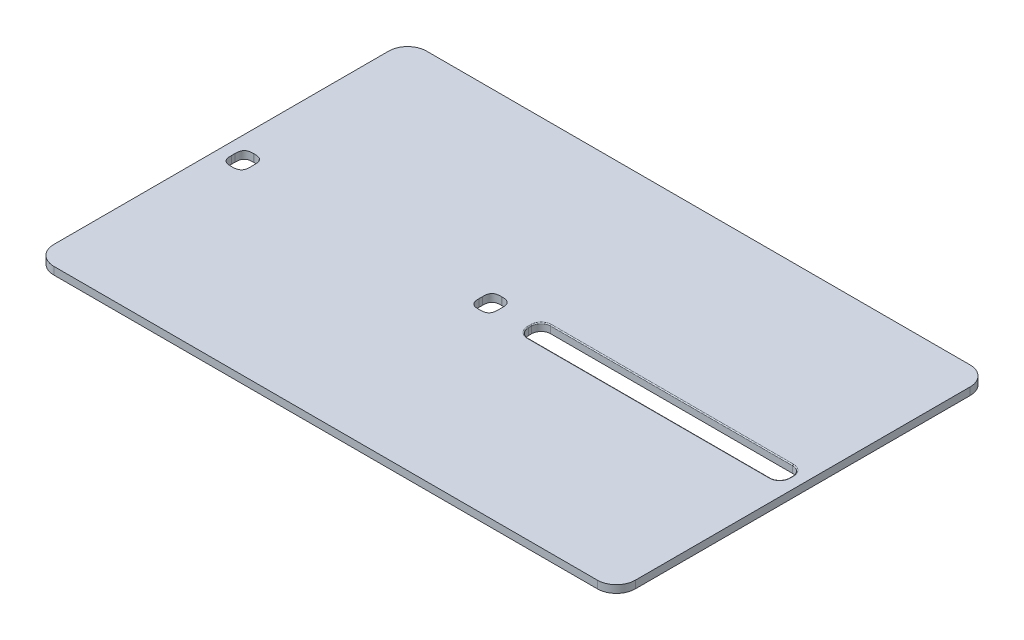
SolidWorks part; units mm, degrees
ref_plane "Front Plane" through (0, 0, 0) normal (0, 0, 1) x (1, 0, 0)
ref_plane "Top Plane" through (0, 0, 0) normal (0, 1, 0) x (1, 0, 0)
ref_plane "Right Plane" through (0, 0, 0) normal (1, 0, 0) x (0, 0, -1)
sketch "Sketch1" plane through (0, 0, 0) normal (0, 1, 0) x (1, 0, 0)
  line L1 (0, 0) -> (78, 0)
  line L2 (0, 0) -> (0, 50)
  line L3 (0, 50) -> (78, 50)
  line L4 (78, 0) -> (78, 50)
  dimension "D1" = 78
  dimension "D2" = 50
extrude "steel_face" add sketch "Sketch1" along normal blind 1.016
fillet "card_edges" radius 2.54 4 edges at (0, 0.508, -50) (78, 0.508, -50) (78, 0.508, 0) (0, 0.508, 0)
sketch "Sketch2" plane through (0, 0, 0) normal (0, -1, 0) x (1, 0, 0)
  line L2 (0, -47.46) -> (0, -2.54) construction
  line L4 (75.46, -50) -> (2.54, -50) construction
  circle A0 centre (4.1275, -45.8725) radius 2.54
  dimension "D1" = 5.08
  dimension "D2" = 1.5875
  dimension "D3" = 1.5875
extrude "magnet_cavity" cut sketch "Sketch2" against normal blind 0.3334
ref_plane "Plane1" through (39, 0, 0) normal (1, 0, 0) x (0, 0, -1)
ref_plane "Plane2" through (0, 0, -25) normal (0, 0, 1) x (1, 0, 0)
mirror "Mirror1" about plane through (0, 0, -25) normal (0, 0, 1) of "magnet_cavity"
mirror "Mirror2" about plane through (39, 0, 0) normal (1, 0, 0) of "Mirror1"
sketch "Sketch3" plane through (0, 0, 0) normal (0, -1, 0) x (1, 0, 0)
  line L0 (2.54, 0) -> (75.46, 0) construction
  line L1 (0, -47.46) -> (0, -2.54) construction
  line L4 (75.46, -50) -> (2.54, -50) construction
  circle A0 centre (16.4, -11.6375) radius 10.05
  circle A1 centre (16.4, -38.3625) radius 10.05
  point P4 (16.4, -36.1176)
  point P5 (14.1387, -35.921)
  point P6 (16.4, -36.5106)
  point P7 (16.4, -37.4334)
  dimension "D2" = 1.5875
  dimension "D1" = 20.1
  dimension "D3" = 6.35
  dimension "D4" = 1.5875
extrude "battery_pockets" cut sketch "Sketch3" against normal blind 0.873
sketch "Sketch5" plane through (0, 0, 0) normal (0, 1, 0) x (1, 0, 0)
  line L0 (78, 2.54) -> (78, 47.46) construction
  line L1 (76.4125, 26.5) -> (41.4125, 26.5)
  line L2 (76.4125, 26.5) -> (76.4125, 23.5)
  line L3 (76.4125, 23.5) -> (41.4125, 23.5)
  line L4 (41.4125, 26.5) -> (41.4125, 23.5)
  line L5 (-0.6138, 25) -> (0.6138, 25) construction
  dimension "D1" = 1.5875
  dimension "D2" = 3
  dimension "D3" = 35
  dimension "D4" = 1.5
extrude "led_slot" cut sketch "Sketch5" along direction (0, -1, 0) on the side of the normal through all
sketch "Sketch4" plane through (0, 0, 0) normal (0, -1, 0) x (1, 0, 0)
  line L0 (7.4613, -48.4125) -> (7.4613, -42.5388)
  line L1 (7.4613, -48.4125) -> (70.5387, -48.4125)
  line L2 (70.5387, -48.4125) -> (70.5387, -42.5388)
  line L3 (1.5875, -27.9199) -> (76.476, -27.9199)
  line L4 (7.4613, -42.5388) -> (1.5875, -42.5388)
  line L5 (1.5875, -42.5388) -> (1.5875, -27.9199)
  line L6 (70.5387, -42.5388) -> (76.476, -42.5388)
  line L7 (76.476, -27.9199) -> (76.476, -42.5388)
  line L8 (0, -47.46) -> (0, -2.54) construction
  line L9 (78, -2.54) -> (78, -47.46) construction
  circle A1 centre (4.1275, -45.8725) radius 2.54 construction
  circle A2 centre (73.8725, -45.8725) radius 2.54 construction
  circle A3 centre (4.1275, -45.8725) radius 2.54 construction
  circle A6 centre (73.8725, -45.8725) radius 2.54 construction
  point P0 (4.1275, -45.8725)
  point P1 (73.8725, -45.8725)
  dimension "D1" = 1.5875
  dimension "D2" = 1.524
  dimension "D3" = 0.7937
  dimension "D4" = 0.7937
  dimension "D5" = 0.7937
  dimension "D6" = 0.7937
extrude "aluminium_inset_hole" [suppressed] cut sketch "Sketch4" against normal through all
fillet "Fillet1" [suppressed] radius 2.54
fillet "led_slot_corner_round" radius 1.27 4 edges at (41.4125, 0.508, -26.5) (41.4125, 0.508, -23.5) (76.4125, 0.508, -26.5) (76.4125, 0.508, -23.5)
fillet "led_slot_surface_round" radius 0.127 8 edges at (76.0405, 1.016, -23.872) (76.4125, 1.016, -25) (76.0405, 1.016, -26.128) (58.9125, 1.016, -23.5) (41.7845, 1.016, -23.872) (41.4125, 1.016, -25) (41.7845, 1.016, -26.128) (58.9125, 1.016, -26.5)
sketch "Sketch6" plane through (0, 0, 0) normal (0, -1, 0) x (1, 0, 0)
  line L0 (0.6138, -25) -> (-0.6138, -25) construction
  line L1 (1.5875, -23.5) -> (4.1875, -23.5)
  line L2 (1.5875, -23.5) -> (1.5875, -26.5)
  line L3 (1.5875, -26.5) -> (4.1875, -26.5)
  line L4 (4.1875, -23.5) -> (4.1875, -26.5)
  line L5 (0, -47.46) -> (0, -2.54) construction
  point P4 (1.5875, -25)
  dimension "D3" = 1.5875
  dimension "D2" = 3
  dimension "D1" = 2.6
extrude "als_data_sensor_slot" cut sketch "Sketch6" against normal through all
sketch "Sketch8" plane through (0, 0, 0) normal (0, -1, 0) x (1, 0, 0)
  line L1 (34.8125, -23.5) -> (37.4125, -23.5)
  line L2 (34.8125, -23.5) -> (34.8125, -26.5)
  line L3 (34.8125, -26.5) -> (37.4125, -26.5)
  line L4 (37.4125, -23.5) -> (37.4125, -26.5)
  line L6 (0.6138, -25) -> (-0.6138, -25) construction
  line L8 (39, -0.6138) -> (39, 0.6138) construction
  point P4 (34.8125, -25)
  dimension "D3" = 1.5875
  dimension "D2" = 3
  dimension "D1" = 2.6
extrude "als_clock_sensor_slot" cut sketch "Sketch8" against normal through all
fillet "Fillet4" radius 1.27 8 edges at (1.5875, 0.508, -26.5) (4.1875, 0.508, -26.5) (1.5875, 0.508, -23.5) (4.1875, 0.508, -23.5) (34.8125, 0.508, -26.5) (34.8125, 0.508, -23.5) (37.4125, 0.508, -26.5) (37.4125, 0.508, -23.5) curvature continuous yes
equation "\"magnet_diameter\" = 0.2in"
equation "\"D1@Sketch2\"=\"magnet_diameter\""
equation "\"magnet_inset\"= 0.0625in"
equation "\"magnet_thickness\" = 0.03125in"
equation "\"face_thickness\"= 0.040in"
equation "\"kapton_thickness\"= 0.005in"
equation "\"D1@magnet_cavity\"=(\"magnet_thickness\"/2) - (\"kapton_thickness\"/2)"
equation "\"steel_inset_distance\" = 1in / 32"
equation "\"pcb_thickness\"= 0.6mm"
equation "\"D2@Sketch2\"=\"magnet_inset\""
equation "\"D3@Sketch2\"=\"magnet_inset\""
equation "\"edge_radius\" = 1in / 10"
equation "\"card_width\" = 78mm"
equation "\"card_height\" = 50mm"
equation "\"battery_diameter\" = 20mm"
equation "\"battery_oversize\" = 0.1mm"
equation "\"battery_vertical_inset\" = 1in / 16"
equation "\"battery_horizontal_inset\" = 1in / 4"
equation "\"battery_spacing\" = 1in / 16"
equation "\"D1@Plane1\"=\"card_width\"/2"
equation "\"D1@Plane2\"=\"card_height\"/2"
equation "\"D1@Sketch3\"=\"battery_diameter\"+\"battery_oversize\""
equation "\"D2@Sketch3\"=\"battery_vertical_inset\""
equation "\"battery_thickness\" = 1.6mm"
equation "\"D1@battery_pockets\" = \"face_thickness\" -  ( \"pcb_thickness\" + \"kapton_thickness\" + \"face_thickness\" - \"battery_thickness\" ) "
equation "\"D3@Sketch3\"=\"battery_horizontal_inset\""
equation "\"battery_cap_oversize\" = 1in / 16"
equation "\"battery_cap_thickness\" = 0.005in"
equation "\"led_strip_height\" = 3mm"
equation "\"led_strip_width\" = 35mm"
equation "\"led_strip_inset\" = 1in / 16"
equation "\"D1@Sketch5\"=\"led_strip_inset\""
equation "\"D2@Sketch5\"=\"led_strip_height\""
equation "\"D3@Sketch5\"=\"led_strip_width\""
equation "\"D4@Sketch5\"=\"led_strip_height\"/2"
equation "\"D1@Sketch4\"=\"magnet_inset\""
equation "\"D3@Sketch4\"=\"magnet_inset\"/2"
equation "\"D4@Sketch4\"=\"magnet_inset\"/2"
equation "\"D5@Sketch4\"=\"magnet_inset\"/2"
equation "\"D6@Sketch4\"=\"magnet_inset\"/2"
equation "\"D1@Fillet1\"=\"magnet_diameter\"/2"
equation "\"D4@Sketch3\"=\"battery_vertical_inset\""
equation "\"max_component_thickness\" = 1mm"
equation "\"als_component_group_width\" = 2.6mm"
equation "\"als_component_group_height\" = 2.6mm"
equation "\"als_data_component_group_edge_inset\" = 0.0625in"
equation "\"als_clock_component_group_edge_inset\" = 1in"
equation "\"als_sensor_width\" = 2.6mm"
equation "\"als_sensor_height\" = 3mm"
equation "\"als_data_sensor_edge_inset\" = 0.0625in"
equation "\"als_clock_sensor_edge_inset\" = 1in"
equation "\"D1@Sketch6\"=\"als_sensor_width\""
equation "\"D2@Sketch6\"=\"als_sensor_height\""
equation "\"D3@Sketch6\"=\"als_data_sensor_edge_inset\""
equation "\"D1@Sketch8\"=\"als_sensor_width\""
equation "\"D2@Sketch8\"=\"als_sensor_height\""
equation "\"D3@Sketch8\"=\"als_data_sensor_edge_inset\""
